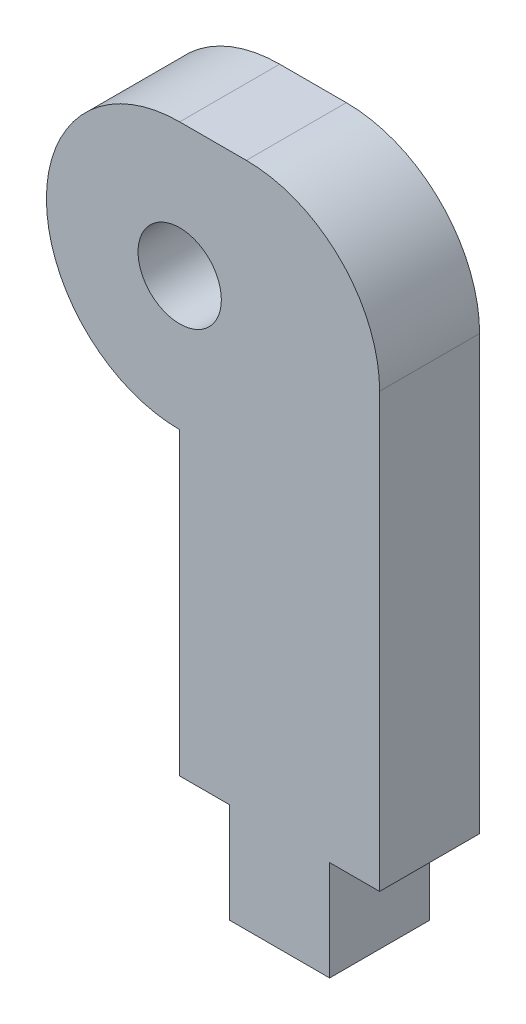
SolidWorks part; units mm, degrees
ref_plane "Front Plane" through (0, 0, 0) normal (0, 0, 1) x (1, 0, 0)
ref_plane "Top Plane" through (0, 0, 0) normal (0, 1, 0) x (1, 0, 0)
ref_plane "Right Plane" through (0, 0, 0) normal (1, 0, 0) x (0, 0, -1)
sketch "Sketch2" plane through (0, 0, 0) normal (0, 0, 1) x (1, 0, 0)
  line L0 (0, 38.3401) -> (0, -59.8736) construction
  line L1 (6, 4) -> (6, -13)
  line L2 (6, -13) -> (4.5, -13)
  line L3 (4.5, -13) -> (4.5, -16)
  line L4 (4.5, -16) -> (1.5, -16)
  line L5 (1.5, -16) -> (1.5, -13)
  line L6 (1.5, -13) -> (0, -13)
  line L7 (0, -13) -> (0, -4)
  line L8 (0, 4) -> (6, 4)
  line L10 (6, 38.3401) -> (6, -59.8736) construction
  arc A0 (0, 4) -> (0, -4) centre (0, 0) ccw
  circle A1 centre (0, 0) radius 1.25
  dimension "D2" = 2.5
  dimension "D3" = 8
  dimension "D4" = 0
  dimension "D5" = 17
  dimension "D6" = 3
  dimension "D7" = 1.5
  dimension "D8" = 3
  dimension "D1" = 6
extrude "Boss-Extrude1" add sketch "Sketch2" along normal blind 3
fillet "Fillet1" radius 4 1 edges at (6, 4, 1.5)
